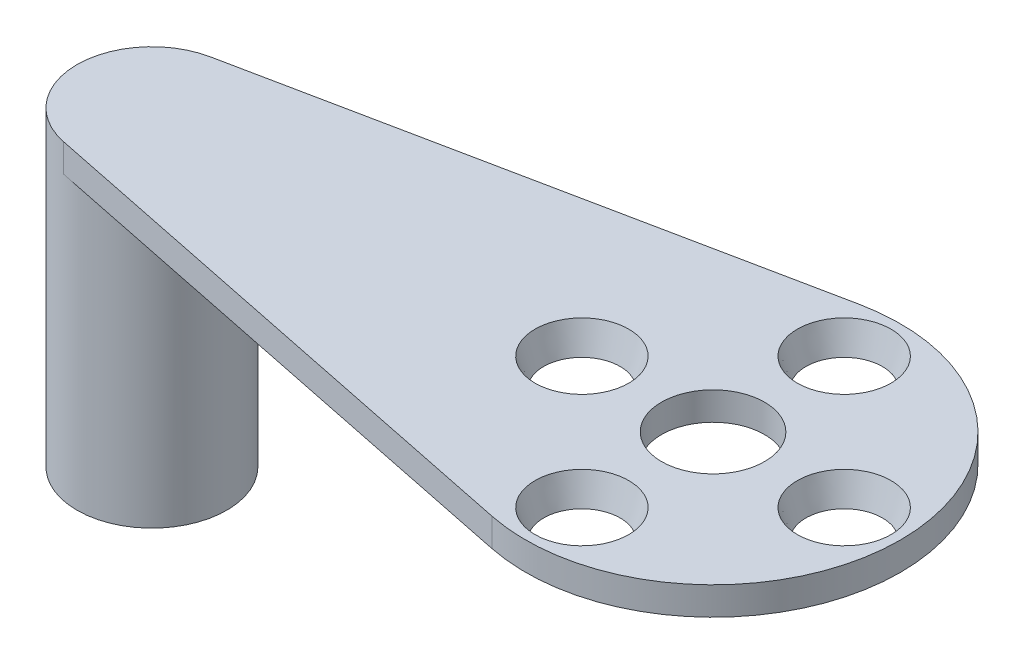
SolidWorks part; units mm, degrees
ref_plane "Front Plane" through (0, 0, 0) normal (0, 0, 1) x (1, 0, 0)
ref_plane "Top Plane" through (0, 0, 0) normal (0, 1, 0) x (1, 0, 0)
ref_plane "Right Plane" through (0, 0, 0) normal (1, 0, 0) x (0, 0, -1)
sketch "Croquis1" plane through (0, 0, 0) normal (0, 1, 0) x (1, 0, 0)
  line L0 (-0.8013, 3.9189) -> (27.9467, 9.7973)
  line L3 (-0.8013, -3.9189) -> (27.9467, -9.7973)
  arc A1 (27.9467, -9.7973) -> (27.9467, 9.7973) centre (29.95, 0) ccw
  arc A4 (-0.8013, 3.9189) -> (-0.8013, -3.9189) centre (0, 0) ccw
  circle A5 centre (29.95, 7) radius 1.6
  circle A7 centre (36.95, 0) radius 1.6
  circle A8 centre (29.95, -7) radius 1.6
  circle A9 centre (22.95, 0) radius 1.6
  circle A10 centre (29.95, 0) radius 2.75
  dimension "D1" = 20
  dimension "D3" = 8
  dimension "D5" = 3.2
  dimension "D7" = 5.5
  dimension "D2" = 29.95
  dimension "D4" = 7
  dimension "D6" = 4
extrude "Saliente-Extruir1" add sketch "Croquis1" along normal blind 1.5
sketch "Croquis3" plane through (0, 0, 0) normal (0, -1, 0) x (1, 0, 0)
  circle A3 centre (0, 0) radius 4
  arc A4 (-0.8013, 3.9189) -> (-0.8013, -3.9189) centre (0, 0) ccw construction
extrude "Saliente-Extruir3" add sketch "Croquis3" along normal offset from surface (15.1 mm away) 16.6 up to face at (29.95, 1.5, 8.6)
sketch "Croquis4" plane through (0, -15.1, 0) normal (0, -1, 0) x (1, 0, 0)
  circle A0 centre (0, 0) radius 2.5
  circle A1 centre (0, 0) radius 3.1
  dimension "D1" = 5
  dimension "D2" = 6.2
extrude "Cortar-Extruir1" cut sketch "Croquis4" against normal blind 7.87 contours A1
extrude "Saliente-Extruir4" add sketch "Croquis4<3>" against normal offset from surface (6.17 mm away) 0.85 from offset 0.85 up to face at (0, -7.23, -3.1) offset against normal yes
sketch "Croquis4<3>" plane through (0, -15.1, 0) normal (0, -1, 0) x (1, 0, 0) same geometry as "Croquis4"
sketch "Croquis5" plane through (0, 1.5, 0) normal (0, 1, 0) x (1, 0, 0)
  circle A0 centre (29.95, 7) radius 2.5
  circle A1 centre (29.95, 0) radius 10
  arc A2 (27.9467, -9.7973) -> (27.9467, 9.7973) centre (29.95, 0) ccw construction
  circle A3 centre (36.95, 0) radius 2.5
  circle A4 centre (29.95, -7) radius 2.5
  circle A5 centre (22.95, 0) radius 2.5
  dimension "D1" = 5
  dimension "D2" = 4
extrude "Cortar-Extruir3" cut sketch "Croquis5" against normal blind 1.5 draft 17 contours A4 | A3 | A0 | A5
